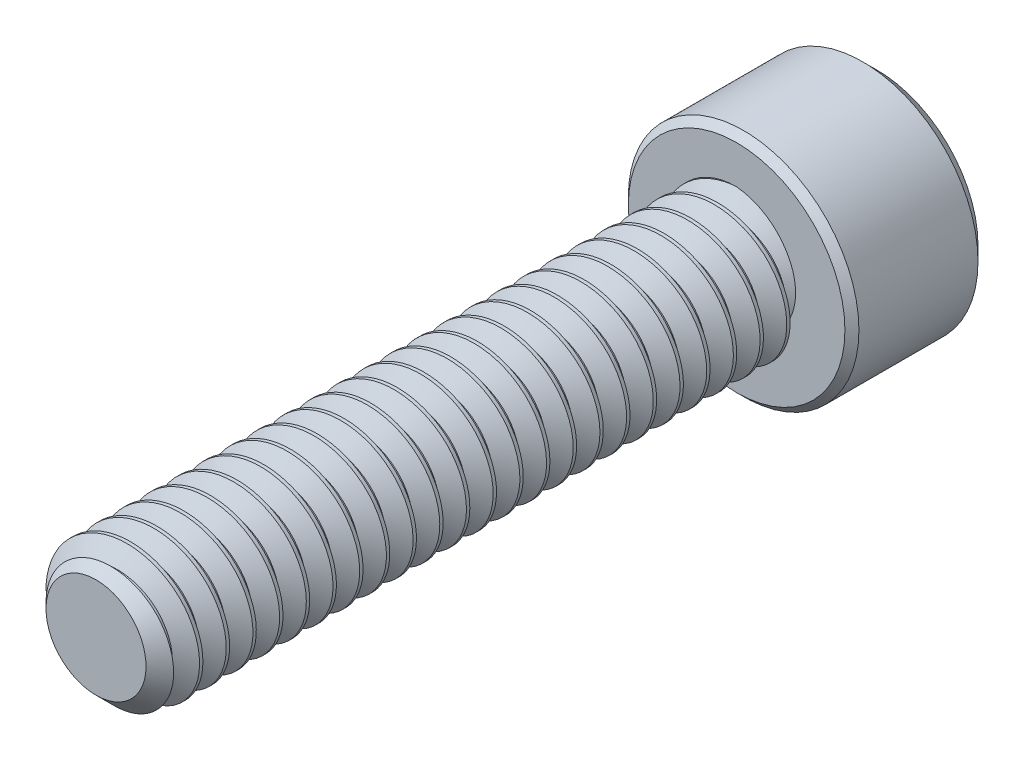
SolidWorks part; units mm, degrees
material "Cast Alloy Steel"
ref_plane "Front Plane" through (0, 0, 0) normal (0, 0, 1) x (1, 0, 0)
ref_plane "Top Plane" through (0, 0, 0) normal (0, 1, 0) x (1, 0, 0)
ref_plane "Right Plane" through (0, 0, 0) normal (1, 0, 0) x (0, 0, -1)
sketch "Sketch1" plane through (0, 0, 0) normal (0, 0, 1) x (1, 0, 0)
  line L0 (0, 2.0828) -> (0, -2.0828) construction
  circle A0 centre (0, 0) radius 2.0828
  dimension "OD" = 4.1656
extrude "Extrude1" add sketch "Sketch1" against normal blind 19.05
sketch "Sketch2" plane through (0, 0, 0) normal (0, 0, 1) x (1, 0, 0)
  circle A0 centre (0, 0) radius 2.0828 construction
  circle A1 centre (0, 0) radius 2.0828
curve "Helix/Spiral1" pitch 0.7937 height 19.8438 turns 25 parameters "pitch"=0.7937
chamfer "Chamfer3" distance 0.5953 angle 45 1 edges at (2.0828, 0, 0)
sketch "Sketch3" plane through (0, 0, 0) normal (1, 0, 0) x (0, 0, -1)
  line L0 (-0.6945, 2.0828) -> (-0.3969, 1.5672)
  line L1 (-0.3969, 1.5672) -> (-0.2977, 1.5672)
  line L2 (-0.2977, 1.5672) -> (0, 2.0828)
  line L3 (-0.6945, 2.0828) -> (0, 2.0828)
  line L4 (-0.3473, 2.0828) -> (-0.3473, 1.5672) construction
  line L5 (-0.5457, 1.825) -> (-0.1488, 1.825) construction
  line L6 (0, 2.0828) -> (0, -2.0828) construction
  dimension "D1" = 0.0992
  dimension "D2" = 0.3969
  dimension "D3" = 60
sweep "Cut-Sweep1" cut profiles "Sketch3" path "Helix/Spiral1"
sketch "Sketch6" plane through (0, 0, -19.05) normal (0, 0, -1) x (-1, 0, 0)
  circle A0 centre (0, 0) radius 3.429
  dimension "head dia" = 6.858
extrude "Extrude2" add sketch "Sketch6" along normal blind 4.1656
sketch "Sketch7" plane through (0, 0, -23.2156) normal (0, 0, -1) x (-1, 0, 0)
  line L1 (0, 2.0622) -> (-1.7859, 1.0311)
  line L2 (-1.7859, 1.0311) -> (-1.7859, -1.0311)
  line L3 (-1.7859, -1.0311) -> (0, -2.0622)
  line L4 (0, -2.0622) -> (1.7859, -1.0311)
  line L5 (1.7859, -1.0311) -> (1.7859, 1.0311)
  line L6 (1.7859, 1.0311) -> (0, 2.0622)
  circle A0 centre (0, 0) radius 1.7859 construction
  dimension "hex dia" = 3.5719
extrude "Cut-Extrude1" cut sketch "Sketch7" against normal blind 2.6789
sketch "Sketch8" plane through (0, 0, -23.2156) normal (0, 0, -1) x (-1, 0, 0)
  circle A0 centre (0, 0) radius 2.0622
extrude "Cut-Extrude2" cut sketch "Sketch8" against normal blind 0.4166 draft 45
chamfer "Chamfer1" distance 0.4166 angle 45 1 edges at (-3.429, 0, -23.2156)
chamfer "Chamfer2" distance 0.2083 angle 45 1 edges at (-3.429, 0, -19.05)
sketch "Sketch9" plane through (0, 0, 0) normal (1, 0, 0) x (0, 0, -1)
  line L0 (0, 2.0828) -> (0, -2.0828) construction
  line L1 (4.3656, 2.0828) -> (4.3656, -2.0828) construction
  line L2 (19.05, 3.429) -> (19.05, -3.429) construction
  line L3 (23.2156, 3.429) -> (23.2156, -3.429) construction
  line L4 (23.2156, 0) -> (0, 0) construction
  dimension "D1" = 4.3656
  dimension "D2" = 4.1656
  dimension "D3" = 6.858
  dimension "D4" = 19.05
equation "\"D3@Helix/Spiral1\" = \"screw length@Extrude1\"+\"pitch@Helix/Spiral1\""
equation "\"D1@Sketch3\" = \"pitch@Helix/Spiral1\"*.125"
equation "\"D2@Sketch3\" = \"pitch@Helix/Spiral1\"*.5"
equation "\"D1@Cut-Extrude1\" = \"hex dia@Sketch7\"*.75"
equation "\"D1@Chamfer1\" = \"head depth@Extrude2\"/10"
equation "\"D1@Sketch9\" = \"pitch@Helix/Spiral1\"*5.5"
equation "\"D1@Chamfer2\" = \"D1@Chamfer1\"/2"
equation "\"D1@Cut-Extrude2\" = \"D1@Chamfer2\"*2"
equation "\"D1@Chamfer3\" = \"pitch@Helix/Spiral1\"*.750"
equation "\"D2@Sketch9\" = \"head depth@Extrude2\""
equation "\"D3@Sketch9\" = \"head dia@Sketch6\""
equation "\"D4@Sketch9\" = \"screw length@Extrude1\""
